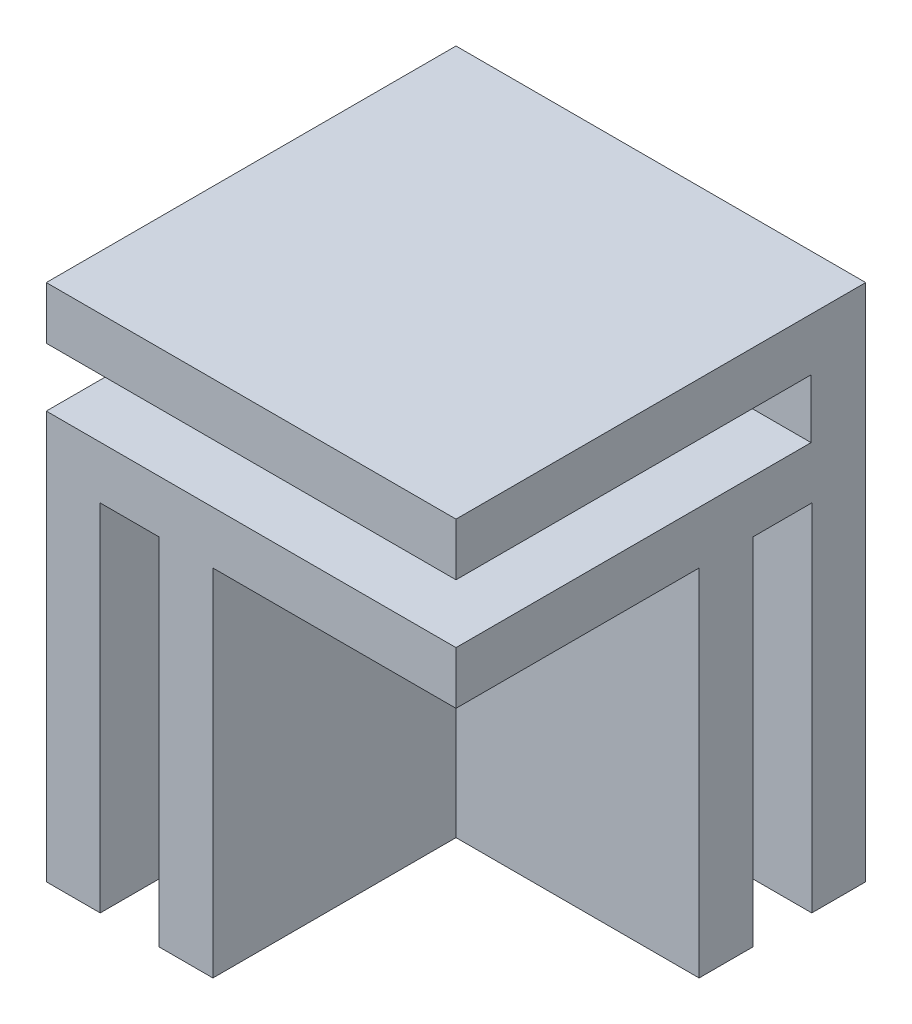
SolidWorks part; units mm, degrees
ref_plane "Plan de face" through (0, 0, 0) normal (0, 0, 1) x (1, 0, 0)
ref_plane "Plan de dessus" through (0, 0, 0) normal (0, 1, 0) x (1, 0, 0)
ref_plane "Plan de droite" through (0, 0, 0) normal (1, 0, 0) x (0, 0, -1)
sketch "Esquisse1" plane through (0, 0, 0) normal (0, 1, 0) x (1, 0, 0)
  line L1 (-35.8867, 13.5315) -> (-5.8867, 13.5315)
  line L2 (-35.8867, 13.5315) -> (-35.8867, -16.4685)
  line L3 (-35.8867, -16.4685) -> (-5.8867, -16.4685)
  line L4 (-5.8867, 13.5315) -> (-5.8867, -16.4685)
  dimension "D1" = 30
  dimension "D2" = 30
extrude "Boss.-Extru.1" add sketch "Esquisse1" along normal blind 38
sketch "Esquisse2" plane through (0, 0, 0) normal (0, -1, 0) x (1, 0, 0)
  line L0 (-5.8867, 16.4685) -> (-5.8867, -13.5315) construction
  line L1 (-5.8867, -9.5815) -> (-23.6867, -9.5815)
  line L2 (-5.8867, -9.5815) -> (-5.8867, -5.2815)
  line L3 (-5.8867, -5.2815) -> (-23.6867, -5.2815)
  line L4 (-23.6867, -9.5815) -> (-23.6867, -5.2815)
  line L5 (-35.8867, 16.4685) -> (-5.8867, 16.4685) construction
  line L6 (-27.6367, 16.4685) -> (-31.9367, 16.4685)
  line L7 (-27.6367, 16.4685) -> (-27.6367, -1.3315)
  line L8 (-27.6367, -1.3315) -> (-31.9367, -1.3315)
  line L9 (-31.9367, 16.4685) -> (-31.9367, -1.3315)
  line L15 (-35.8867, -13.5315) -> (-35.8867, 16.4685) construction
  line L16 (-5.8867, -13.5315) -> (-35.8867, -13.5315) construction
  line L18 (-5.8867, 16.4685) -> (-23.6867, 16.4685)
  line L19 (-5.8867, 16.4685) -> (-5.8867, -1.3315)
  line L20 (-5.8867, -1.3315) -> (-23.6867, -1.3315)
  line L21 (-23.6867, 16.4685) -> (-23.6867, -1.3315)
  dimension "D1" = 4.3
  dimension "D2" = 17.8
  dimension "D3" = 3.95
  dimension "D4" = 4.3
  dimension "D5" = 17.8
  dimension "D6" = 3.95
  dimension "D7" = 3.95
  dimension "D8" = 3.95
extrude "Enlèv. mat.-Extru.1" cut sketch "Esquisse2" against normal blind 26
sketch "Esquisse5" plane through (-35.8867, 0, 0) normal (-1, 0, 0) x (0, 0, 1)
  line L0 (16.4685, 38) -> (16.4685, 0) construction
  line L1 (16.4685, 34.15) -> (-9.5315, 34.15)
  line L2 (16.4685, 34.15) -> (16.4685, 29.85)
  line L3 (16.4685, 29.85) -> (-9.5315, 29.85)
  line L4 (-9.5315, 34.15) -> (-9.5315, 29.85)
  line L5 (-13.5315, 38) -> (-13.5315, 0) construction
  line L6 (-13.5315, 38) -> (16.4685, 38) construction
  dimension "D1" = 4
  dimension "D2" = 4.3
  dimension "D3" = 3.85
extrude "Enlèv. mat.-Extru.4" cut sketch "Esquisse5" against normal through all
